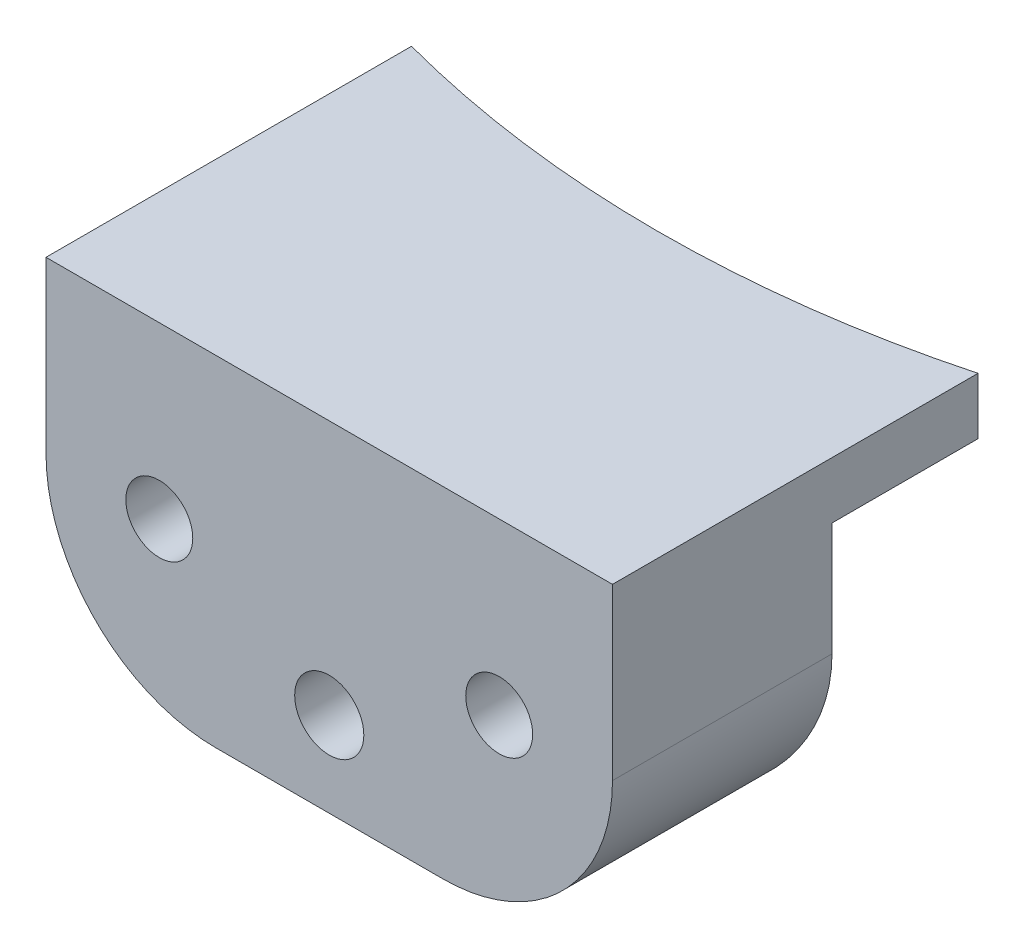
SolidWorks part; units mm, degrees
note: The reader was unsure of these and kept them because the rebuilt part matched: shared geometry of "Sketch2<4>".
material "6061 Alloy"
ref_plane "Front Plane" through (0, 0, 0) normal (0, 0, 1) x (1, 0, 0)
ref_plane "Top Plane" through (0, 0, 0) normal (0, 1, 0) x (1, 0, 0)
ref_plane "Right Plane" through (0, 0, 0) normal (1, 0, 0) x (0, 0, -1)
sketch "Sketch1" plane through (0, 0, 0) normal (0, 1, 0) x (1, 0, 0)
  line L0 (-12.7, -54.0916) -> (-12.7, -57.3481)
  line L1 (12.7, -54.0916) -> (12.7, -57.3481)
  line L2 (-12.7, -58.8541) -> (12.7, -58.8541)
  line L3 (-12.7, -57.3481) -> (-12.7, -58.8541)
  line L4 (12.7, -57.3481) -> (12.7, -58.8541)
  line L5 (0, -58.7375) -> (21.9276, -58.7375)
  circle A0 centre (0, 0) radius 55.5625
  circle A1 centre (0, 0) radius 58.7375
  dimension "D1" = 111.125
  dimension "D3" = 12.7
  dimension "D4" = 12.7
  dimension "D5" = 4.7625
  dimension "D6" = 0.1166
  dimension "D2" = 3.175
extrude "Boss-Extrude1" add sketch "Sketch1" along normal blind 12.7 contours L0 A1 L1 A0 | A1 L3 L2 | A1 L2 L4
sketch "Sketch2" plane through (0, 0, 0) normal (0, 0, 1) x (1, 0, 0)
  line L0 (0, 12.7) -> (0, 0) construction
  line L5 (-12.7, 0) -> (12.7, 0)
  line L6 (12.7, 0) -> (12.7, 12.7)
  line L7 (12.7, 12.7) -> (-12.7, 12.7)
  line L12 (-12.7, 12.7) -> (-12.7, 0)
  line L13 (-12.7, 0) -> (12.7, 0)
  line L14 (12.7, 0) -> (12.7, 12.7)
  line L15 (12.7, 12.7) -> (-12.7, 12.7)
  line L16 (-12.7, 12.7) -> (-12.7, 0)
  circle A0 centre (-7.62, 7.62) radius 1.5
  circle A1 centre (0, 3.81) radius 1.55
  dimension "D6" = 3
  dimension "D4" = 3.1
  dimension "D5" = 7.62
  dimension "D2" = 7.62
  dimension "D3" = 3.81
  dimension "D7" = 3.81
extrude "Cut-Extrude1" cut sketch "Sketch2" along normal up to surface (58.8541 mm away) contours A0 up to face at (0, 6.35, 58.8541)
mirror "Mirror1" about plane through (0, 0, 0) normal (1, 0, 0) of "Cut-Extrude1"
fillet "Fillet1" radius 7.62 2 edges at (-12.7, 0, 56.4729) (12.7, 0, 56.4729)
extrude "Cut-Extrude2" cut sketch "Sketch2<4>" along normal through all contours A1 L0 | L0 A1
sketch "Sketch2<4>" plane through (0, 0, 0) normal (0, 0, 1) x (1, 0, 0) same geometry as "Sketch2"
sketch "Sketch7" plane through (0, 12.7, 0) normal (0, 1, 0) x (1, 0, 0)
  line L3 (-12.7, -58.8541) -> (12.7, -58.8541)
  line L4 (12.7, -58.8541) -> (12.7, -54.0916)
  line L5 (-12.7, -54.0916) -> (-12.7, -58.8541)
  line L6 (-12.7, -58.8541) -> (12.7, -58.8541)
  line L7 (12.7, -58.8541) -> (12.7, -54.0916)
  line L8 (-12.7, -54.0916) -> (-12.7, -58.8541)
  line L9 (-12.7, -54.0916) -> (-12.7, -47.5456)
  line L10 (12.7, -54.0916) -> (12.7, -47.5456)
  line L11 (-12.7, -58.8541) -> (-12.7, -47.5456)
  line L12 (-19.05, -45.3758) -> (-19.05, -65.2041) construction
  line L13 (-19.05, -65.2041) -> (19.05, -65.2041) construction
  line L14 (19.05, -65.2041) -> (19.05, -45.3758) construction
  line L15 (12.7, -47.5456) -> (12.7, -58.8541)
  line L16 (-12.7, -58.8541) -> (12.7, -58.8541)
  arc A0 (-12.7, -47.5456) -> (12.7, -47.5456) centre (0, 0) ccw
  arc A1 (-12.7, -54.0916) -> (12.7, -54.0916) centre (0, 0) ccw
  arc A2 (-12.7, -54.0916) -> (12.7, -54.0916) centre (0, 0) ccw
  arc A3 (-19.05, -45.3758) -> (19.05, -45.3758) centre (0, 0) ccw construction
  line M11 (-12.7, -58.8541) -> (12.7, -58.8541)
  line M12 (12.7, -58.8541) -> (12.7, -54.0916)
  arc M13 (12.7, -54.0916) -> (-12.7, -54.0916) centre (0, 0) cw
  line M14 (-12.7, -54.0916) -> (-12.7, -58.8541)
  dimension "D1" = 0
  dimension "D2" = 6.35
extrude "Boss-Extrude2" add sketch "Sketch7" along normal blind 2.54 contours M14 M11 M12 M13 | A0 L9 L10 M13
sketch "Sketch8" plane through (0, 0, 58.8541) normal (0, 0, 1) x (1, 0, 0)
  line L4 (-5.08, 0) -> (5.08, 0)
  line L5 (12.7, 7.62) -> (12.7, 15.24)
  line L6 (12.7, 15.24) -> (-12.7, 15.24)
  line L7 (-12.7, 15.24) -> (-12.7, 7.62)
  line L8 (-5.08, 0) -> (5.08, 0)
  line L9 (12.7, 7.62) -> (12.7, 15.24)
  line L10 (12.7, 15.24) -> (-12.7, 15.24)
  line L11 (-12.7, 15.24) -> (-12.7, 7.62)
  circle A0 centre (7.62, 7.62) radius 1.5 construction
  circle A1 centre (0, 3.81) radius 1.55 construction
  arc A2 (5.08, 0) -> (12.7, 7.62) centre (5.08, 7.62) ccw
  arc A3 (-12.7, 7.62) -> (-5.08, 0) centre (-5.08, 7.62) ccw
  arc A4 (5.08, 0) -> (12.7, 7.62) centre (5.08, 7.62) ccw
  arc A5 (-12.7, 7.62) -> (-5.08, 0) centre (-5.08, 7.62) ccw
  circle A6 centre (-7.62, 7.62) radius 1.5 construction
  circle A7 centre (7.62, 7.62) radius 1.5
  circle A8 centre (0, 3.81) radius 1.55
  circle A9 centre (-7.62, 7.62) radius 1.5
  dimension "D1" = 0
extrude "Boss-Extrude3" add sketch "Sketch8" along normal blind 5.08
equation "\"Middle Coupler Inner Daimeter\"= 3.875in"
equation "\"Middle Coupler  Wall Thickness\" = 0.25in"
equation "\"Middle Coupler Bottom Thickness\"= 0.2in"
equation "\"Bearing Rail Offset\"= 0.45in"
equation "\"3-56 UNF Tap\"= 0.089in"
equation "\"3-56 UNF Clearance\"= 0.104in"
equation "\"Ball Bearing Distance\"= 0.03in"
equation "\"TCA Outer Diameter\" = 6in"
equation "\"D1@Sketch1\"=\"Middle Coupler Inner Daimeter\"+0.5"
equation "\"D2@Sketch1\"=1/8"
equation "\"D3@Sketch1\"=0.5"
equation "\"D4@Sketch1\"=\"D3@Sketch1\""
equation "\"D6@Sketch2\"=3mm"
equation "\"Interstage Aeroframe Wall Thickness\" = 0.072in"
equation "\"Compression Spring OD\"= 0.42in"
equation "\"10-24 Tap\"= 0.1495in"
equation "\"10-24 Clearance\"= 0.196in"
equation "\"Lower Stage Fuselage Wall Thickness\" = 0.25in"
equation "\"6-32 Tap\" = 0.107in"
equation "\"1/4-20 Tap\" = 0.201in"
equation "\"3-48 Tap\"= 0.079in"
equation "\"3-48 Clearance\" = 0.104in"
equation "\"6-32 Clearance\" = 0.144in"
equation "\"12-24 Tap\" = 0.177in"
equation "\"D5@Sketch1\"=3/16"
equation "\"4-40 Tap\"= 0.089in"
equation "\"4-40 Clearance\" = 0.116in"
equation "\"12-24 Major Diameter\"= 0.216in"
equation "\"D4@Sketch2\"=3.1mm"
